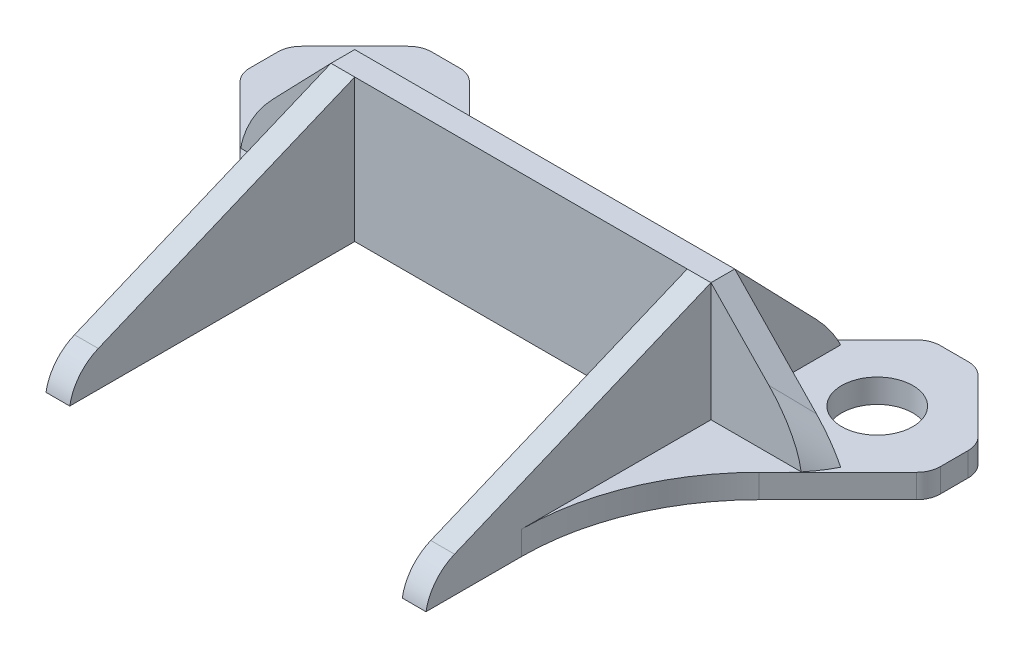
SolidWorks part; units mm, degrees
note: The reader was unsure of these and kept them because the rebuilt part matched: shared geometry of "Sketch5<3>", "Sketch5<4>", "Sketch2<10>".
ref_plane "Front Plane" through (0, 0, 0) normal (0, 0, 1) x (1, 0, 0)
ref_plane "Top Plane" through (0, 0, 0) normal (0, 1, 0) x (1, 0, 0)
ref_plane "Right Plane" through (0, 0, 0) normal (1, 0, 0) x (0, 0, -1)
sketch "Sketch2" plane through (0, 0, 0) normal (0, 1, 0) x (1, 0, 0)
  line L27 (-2.7072, 7.5356) -> (-1, 5.8284)
  line L31 (-6.1214, 6.1214) -> (-4.7072, 7.5356)
  line L32 (-4.7072, 7.5356) -> (-2.7072, 7.5356)
  line L33 (-6.1214, 6.1214) -> (-7.5356, 4.7072)
  line L34 (-7.5356, 4.7072) -> (-7.5356, 2.7072)
  line L36 (-7.5356, 2.7072) -> (-5.8284, 1)
  line L37 (0, -12) -> (-1, -12)
  line L50 (-1, 5.8284) -> (0, 4.8284)
  line L63 (0, -12) -> (0, 0)
  line L64 (-1, -7.9706) -> (-1, -12)
  line L68 (14, 0) -> (0, 0)
  line L75 (19.8284, 1) -> (18.8284, 0)
  line L76 (15, -7.9706) -> (15, -12)
  line L77 (14, -12) -> (14, 0)
  line L87 (-5.8284, 1) -> (-4.8284, 0)
  line L88 (15, 5.8284) -> (14, 4.8284)
  line L90 (14, -12) -> (15, -12)
  line L91 (21.5356, 2.7072) -> (19.8284, 1)
  line L92 (21.5356, 4.7072) -> (21.5356, 2.7072)
  line L93 (20.1214, 6.1214) -> (21.5356, 4.7072)
  line L94 (18.7072, 7.5356) -> (16.7072, 7.5356)
  line L95 (20.1214, 6.1214) -> (18.7072, 7.5356)
  line L96 (16.7072, 7.5356) -> (15, 5.8284)
  line L97 (0, 4.8284) -> (1.3939, 3.4345)
  line L98 (14, 4.8284) -> (12.6061, 3.4345)
  line L99 (-4.8284, 0) -> (-3.9289, -0.8995)
  line L100 (18.8284, 0) -> (17.9289, -0.8995)
  circle A3 centre (-4.0001, 4.0001) radius 1.5
  circle A4 centre (18.0001, 4.0001) radius 1.5
  arc A6 (1.3939, 3.4345) -> (12.6061, 3.4345) centre (7, 9.0406) ccw
  arc A7 (-1, -7.9706) -> (-3.9289, -0.8995) centre (-11, -7.9706) ccw
  arc A8 (15, -7.9706) -> (17.9289, -0.8995) centre (25, -7.9706) cw
  dimension "D2" = 10
  dimension "D10" = 2
  dimension "D3" = 3
  dimension "D4" = 10
  dimension "D5" = 4
  dimension "D6" = 2
  dimension "D11" = 135
  dimension "D12" = 135
extrude "Boss-Extrude5" add sketch "Sketch2" along normal blind 1 contours L27 L50 L97 A6 L98 L88 L96 L94 L95 L93 L92 L91 L75 L100 A8 L76 L90 L77 L68 L63 L37 L64 A7 L99 L87 L36 L34 L33 L31 L32
sketch "Sketch5" plane through (0, 1, 0) normal (0, 1, 0) x (1, 0, 0)
  line L0 (-1, -12) -> (-1, 5.8284)
  line L1 (-4.8284, 0) -> (18.8284, 0)
  line L2 (-5.8284, 1) -> (19.8284, 1)
  line L3 (15, -12) -> (15, 5.8284)
  line L4 (0, 4.8284) -> (0, -12)
  line L5 (0, -12) -> (-1, -12)
  line L6 (-5.8284, 1) -> (-4.8284, 0)
  line L7 (15, 5.8284) -> (14, 4.8284)
  line L8 (14, 4.8284) -> (14, -12)
  line L9 (14, -12) -> (15, -12)
  line L10 (-1, 5.8284) -> (0, 4.8284)
  line L11 (19.8284, 1) -> (18.8284, 0)
extrude "Boss-Extrude6" add sketch "Sketch5" along normal blind 5 contours L1 L11 L2 L6
extrude "Boss-Extrude7" add sketch "Sketch5<3>" along normal blind 5 contours L0 L10 L4 L5
sketch "Sketch5<3>" plane through (0, 1, 0) normal (0, 1, 0) x (1, 0, 0) same geometry as "Sketch5"
extrude "Boss-Extrude8" add sketch "Sketch5<4>" along normal blind 5 contours L8 L9 L3 L7
sketch "Sketch5<4>" plane through (0, 1, 0) normal (0, 1, 0) x (1, 0, 0) same geometry as "Sketch5"
sketch "Sketch6" plane through (-1, 0, 0) normal (-1, 0, 0) x (0, 0, 1)
  line L0 (12, 1) -> (0, 6)
  line L1 (-4.8284, 1) -> (12, 1) construction
  line L2 (0, 6) -> (12, 6)
  line L3 (12, 6) -> (12, 1)
extrude "Cut-Extrude2" cut sketch "Sketch6" against normal through all
sketch "Sketch7" plane through (-1, 0, 0) normal (-1, 0, 0) x (0, 0, 1)
  line L0 (-5.8284, 1) -> (-1, 6)
  line L1 (-5.8284, 1) -> (-5.8284, 6)
  line L2 (-5.8284, 6) -> (-1, 6)
extrude "Cut-Extrude3" cut sketch "Sketch7" against normal through all
sketch "Sketch9" plane through (0, 0, -1) normal (0, 0, -1) x (-1, 0, 0)
  line L0 (5.8284, 1) -> (1, 6)
  line L1 (1, 6) -> (5.8284, 6)
  line L2 (5.8284, 6) -> (5.8284, 1)
  line L3 (-15, 6) -> (-19.8284, 6)
  line L4 (-19.8284, 6) -> (-19.8284, 1)
  line L5 (-19.8284, 1) -> (-15, 6)
extrude "Cut-Extrude4" cut sketch "Sketch9" against normal through all contours L5 L3 L4 | L0 L1 L2
fillet "Fillet1" radius 1 4 edges at (16.7072, 0.5, -7.5356) (21.5356, 0.5, -2.7072) (21.5356, 0.5, -4.7072) (18.7072, 0.5, -7.5356)
extrude "Cut-Extrude5" cut sketch "Sketch2<10>" along normal through all contours A4 | A3
sketch "Sketch2<10>" plane through (0, 0, 0) normal (0, 1, 0) x (1, 0, 0) same geometry as "Sketch2"
fillet "Fillet2" radius 1 4 edges at (-2.7072, 0.5, -7.5356) (-4.7072, 0.5, -7.5356) (-7.5356, 0.5, -4.7072) (-7.5356, 0.5, -2.7072)
fillet "Fillet3" radius 2 6 edges at (14.5, 1.5178, -5.3284) (-0.5, 1.5178, -5.3284) (-5.3284, 1.5178, -0.5) (19.3284, 1.5178, -0.5) (14.5, 1, 12) (-0.5, 1, 12)
